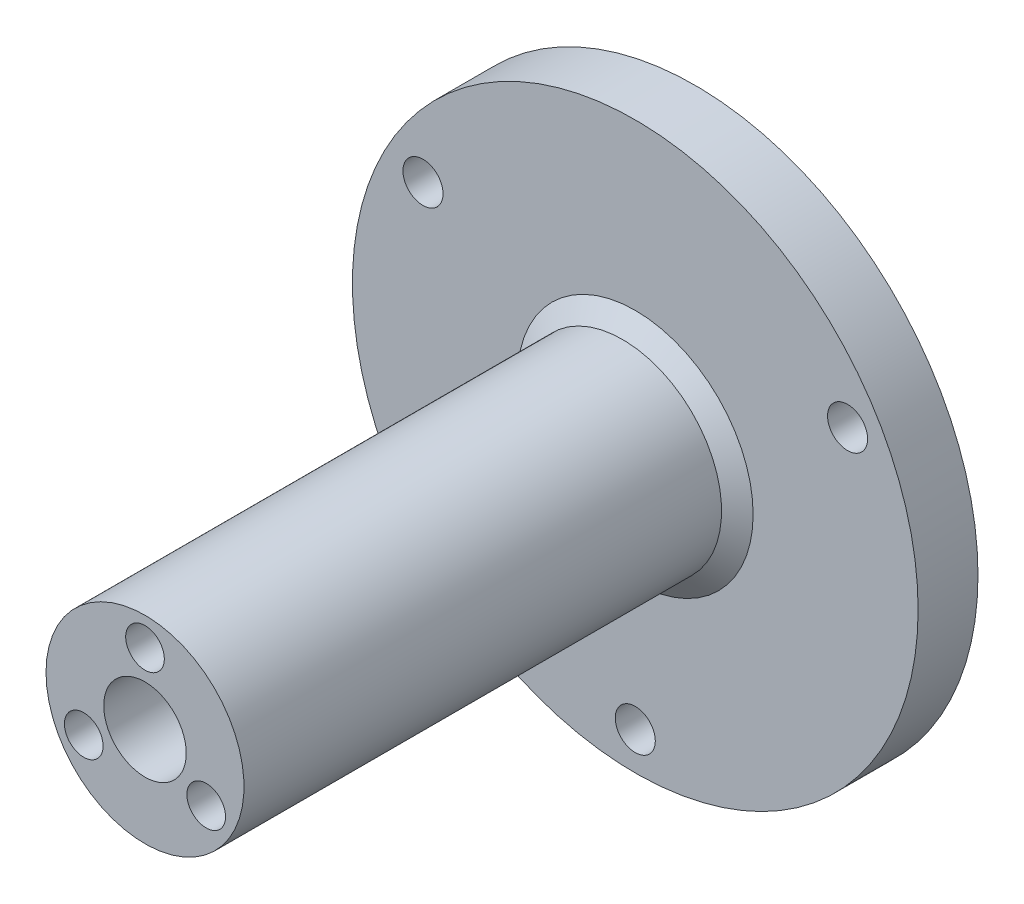
SolidWorks part; units mm, degrees
ref_plane "Plan de face" through (0, 0, 0) normal (0, 0, 1) x (1, 0, 0)
ref_plane "Plan de dessus" through (0, 0, 0) normal (0, 1, 0) x (1, 0, 0)
ref_plane "Plan de droite" through (0, 0, 0) normal (1, 0, 0) x (0, 0, -1)
sketch "Esquisse1" plane through (0, 0, 0) normal (0, 0, 1) x (1, 0, 0)
  line L0 (-17.5, 10.1036) -> (0, -20.2073) construction
  line L1 (0, -20.2073) -> (17.5, 10.1036) construction
  line L2 (17.5, 10.1036) -> (-17.5, 10.1036) construction
  line L3 (16.0524, 9.2678) -> (-8.4583, -4.8834) construction
  line L4 (0.0575, -0.0332) -> (-30.6383, 17.689) construction
  circle A0 centre (-17.5, 10.1036) radius 1.625
  circle A1 centre (0, -20.2073) radius 1.625
  circle A2 centre (17.5, 10.1036) radius 1.625
  dimension "D2" = 3.25
  dimension "D1" = 35
sketch "Esquisse3" plane through (0, 0, 0) normal (0, 0, 1) x (1, 0, 0)
  line L5 (-22.5167, 13) -> (22.5167, 13) construction
  line L6 (22.5167, 13) -> (0, -26) construction
  line L7 (0, -26) -> (-22.5167, 13) construction
  circle A0 centre (-22.5167, 13) radius 2.125
  circle A1 centre (22.5167, 13) radius 2.125
  circle A2 centre (0, -26) radius 2.125
  circle A7 centre (0, 0) radius 26
  circle A8 centre (0, 0) radius 30
  circle A10 centre (0, 0) radius 7.675
  dimension "D2" = 15.35
  dimension "D1" = 52
  dimension "D3" = 60
  dimension "D4" = 4.25
extrude "Boss.-Extru.1" add sketch "Esquisse3" along normal blind 6.35 contours A8 A7 A1 A2 A0 | A1 A7 A0 A2 A10 region at (-20.0113, 14.379, 0) region at (-29.1515, 0, 0)
sketch "Esquisse4" plane through (0, 0, 6.35) normal (0, 0, 1) x (1, 0, 0)
  circle A2 centre (0, 0) radius 7.675
  circle A3 centre (0, 0) radius 10.5
  circle A4 centre (0, 0) radius 7.675 construction
  dimension "D1" = 21
extrude "Boss.-Extru.2" add sketch "Esquisse4" along normal blind 45
sketch "Sketch1" plane through (0, 0, 51.35) normal (0, 0, 1) x (1, 0, 0)
  circle A0 centre (0, 0) radius 10.5
  circle A1 centre (0, 0) radius 4.375
  circle A2 centre (0, 0) radius 10.5 construction
  dimension "D1" = 8.75
extrude "Boss-Extrude1" add sketch "Sketch1" along normal blind 7
sketch "Sketch2" plane through (0, 0, 58.35) normal (0, 0, 1) x (1, 0, 0)
  line L0 (-6.4952, -3.75) -> (0, 7.5) construction
  line L1 (0, 7.5) -> (6.4952, -3.75) construction
  line L2 (-3.2476, 1.875) -> (6.4952, -3.75) construction
  line L3 (-6.4952, -3.75) -> (3.2476, 1.875) construction
  line L4 (-6.4952, -3.75) -> (6.4952, -3.75) construction
  circle A0 centre (0, 7.5) radius 2.05
  circle A1 centre (-6.4952, -3.75) radius 2.05
  circle A2 centre (6.4952, -3.75) radius 2.05
  circle A3 centre (0, 0) radius 7.5
  point P7 (0, 0)
  dimension "D1" = 4.1
  dimension "D2" = 15
extrude "Cut-Extrude1" cut sketch "Sketch2" against normal blind 6 contours A3 A0 | A0 A3 | A3 A1 | A1 A3 | A3 A2 | A2 A3 region at (0, 8.3176, 58.35) region at (0, 6.5815, 58.35) region at (-7.2033, -4.1588, 58.35) region at (-5.6997, -3.2907, 58.35) region at (5.6997, -3.2907, 58.35) region at (7.2033, -4.1588, 58.35)
chamfer "Chamfer2" distance 4 angle 55 1 edges at (7.675, 0, 51.35) first distance on face at (4.375, 0, 51.35)
chamfer "Chamfer3" distance 2 angle 34 1 edges at (10.5, 0, 6.35) first distance on face at (30, 0, 6.35)
